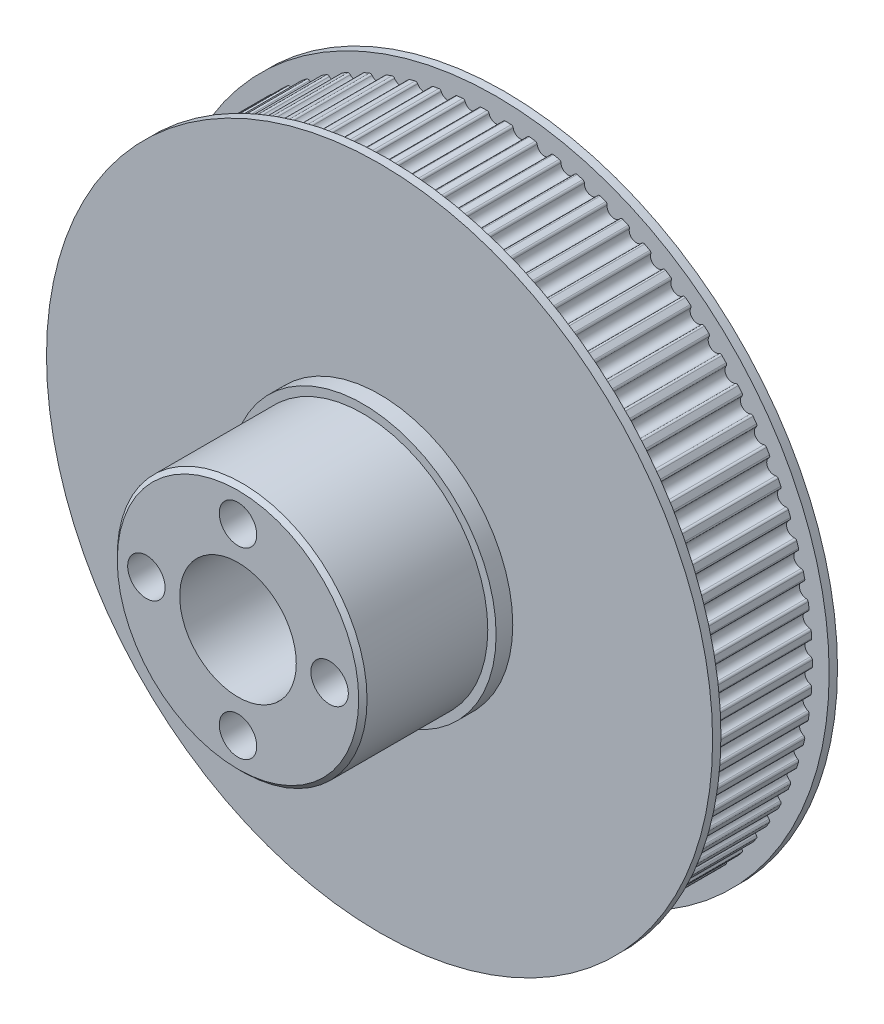
SolidWorks part; units mm, degrees
material "PLA+"
ref_plane "Front Plane" through (0, 0, 0) normal (0, 0, 1) x (1, 0, 0)
ref_plane "Top Plane" through (0, 0, 0) normal (0, 1, 0) x (1, 0, 0)
ref_plane "Right Plane" through (0, 0, 0) normal (1, 0, 0) x (0, 0, -1)
sketch "Sketch1" plane through (0, 0, 0) normal (0, 0, 1) x (1, 0, 0)
  circle A0 centre (0, 0) radius 39.1521 construction
  circle A1 centre (0, 0) radius 37.9821
  dimension "D1" = 78.3042
  dimension "D2" = 1.17
extrude "Boss-Extrude1" add sketch "Sketch1" along normal mid plane 15
sketch "Sketch2" plane through (0, 0, 7.5) normal (0, 0, 1) x (1, 0, 0)
  line L0 (0, 0) -> (0, 37.9821) construction
  circle A0 centre (0, 0) radius 37.9821 construction
  circle A1 centre (0, 37.9821) radius 0.87 construction
  circle A2 centre (-1.0958, 37.7062) radius 0.26 construction
  circle A3 centre (0, 0) radius 37.9821 construction
  arc A4 (-1.1033, 37.9661) -> (-0.8437, 37.7697) centre (-1.0958, 37.7062) cw
  arc A5 (-0.8437, 37.7697) -> (0.8437, 37.7697) centre (0, 37.9821) ccw
  arc A6 (1.1033, 37.9661) -> (0.8437, 37.7697) centre (1.0958, 37.7062) ccw
  arc A7 (-1.1033, 37.9661) -> (1.1033, 37.9661) centre (0, 0) cw
  dimension "D1" = 1.74
  dimension "D2" = 0.52
extrude "Cut-Extrude1" cut sketch "Sketch2" against normal through all both and the other way through all
pattern_circular "CirPattern1" count 82 over 360 about axis through (0, 0, 7.5) along (0, 0, -1) of "Cut-Extrude1"
sketch "Sketch7" plane through (0, 0, 7.5) normal (0, 0, 1) x (1, 0, 0)
  circle A0 centre (0, 0) radius 15
  point P16 (0, 0)
  dimension "D1" = 30
extrude "Boss-Extrude4" add sketch "Sketch7" along normal blind 17
sketch "Sketch8" plane through (0, 0, 7.5) normal (0, 0, 1) x (1, 0, 0)
  circle A0 centre (0, 0) radius 16
  dimension "D1" = 32
extrude "Boss-Extrude5" add sketch "Sketch8" along normal blind 2
sketch "Sketch9" plane through (0, 0, 24.5) normal (0, 0, 1) x (1, 0, 0)
  circle A0 centre (0, 0) radius 7
  circle A1 centre (0, 0) radius 11 construction
  circle A2 centre (0, -11) radius 2.25
  circle A3 centre (-11, 0) radius 2.25
  circle A4 centre (0, 11) radius 2.25
  circle A5 centre (11, 0) radius 2.25
  point P15 (0, 0)
  dimension "D1" = 14
  dimension "D2" = 22
  dimension "D3" = 4.5
  dimension "D4" = 4
extrude "Cut-Extrude2" cut sketch "Sketch9" against normal through all
sketch "Sketch10" plane through (0, 0, -7.5) normal (0, 0, -1) x (-1, 0, 0)
  circle A0 centre (11, 0) radius 3.6
  dimension "D1" = 7.2
extrude "Cut-Extrude3" cut sketch "Sketch10" against normal blind 5
pattern_circular "CirPattern2" count 4 over 360 about axis through (0, 0, -7.5) along (0, 0, 1) of "Cut-Extrude3" reverse direction yes
chamfer "Chamfer1" distance 0.5 angle 45 1 edges at (15, 0, 24.5)
sketch "Sketch11" plane through (0, 0, -7.5) normal (0, 0, -1) x (-1, 0, 0)
  circle A0 centre (0, 0) radius 40
  circle A1 centre (0, 0) radius 7
  circle A2 centre (0, 11) radius 2.25
  circle A3 centre (0, 11) radius 3.6
  circle A4 centre (11, 0) radius 2.25
  circle A5 centre (11, 0) radius 3.6
  circle A6 centre (-11, 0) radius 2.25
  circle A7 centre (-11, 0) radius 3.6
  circle A8 centre (0, -11) radius 2.25
  circle A9 centre (0, -11) radius 3.6
  dimension "D1" = 80
extrude "Boss-Extrude6" add sketch "Sketch11" against normal blind 1 contours A0 A9 A7 A5 A3 A1 region at (38.8686, 0, -7.5)
sketch "Sketch13" plane through (0, 0, 7.5) normal (0, 0, 1) x (1, 0, 0)
  circle A0 centre (0, 0) radius 40
  circle A1 centre (0, 11) radius 2.25
  circle A2 centre (11, 0) radius 2.25
  circle A3 centre (-11, 0) radius 2.25
  circle A4 centre (0, -11) radius 2.25
  circle A5 centre (0, 0) radius 7
  dimension "D1" = 80
extrude "Boss-Extrude7" add sketch "Sketch13" against normal blind 1
equation "\"ๅ\"=1"
